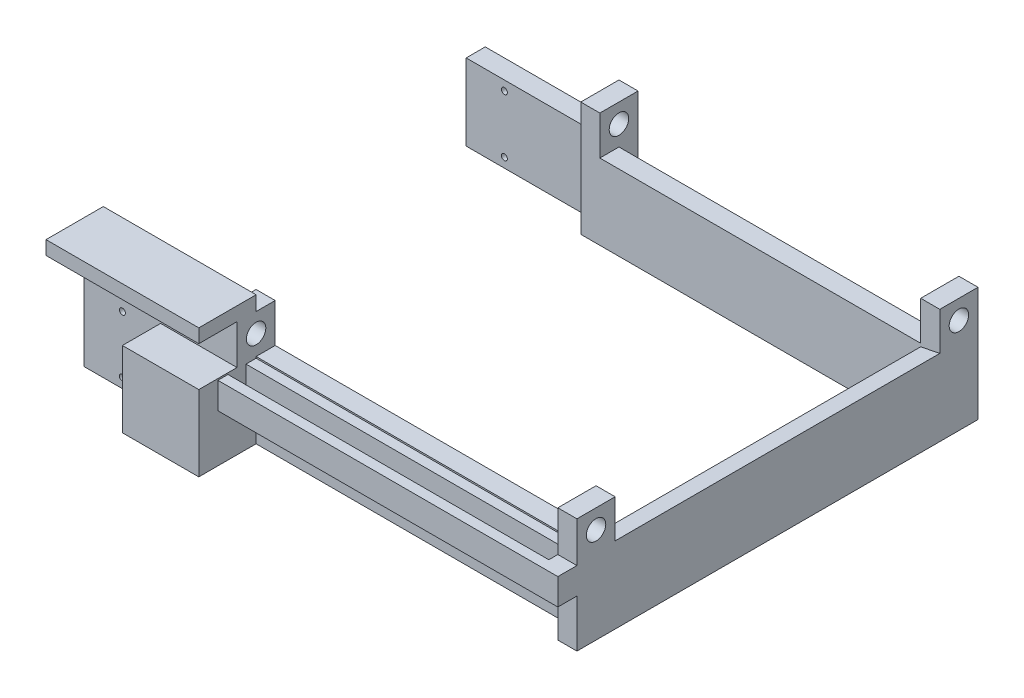
SolidWorks part; units mm, degrees
ref_plane "Front Plane" through (0, 0, 0) normal (0, 0, 1) x (1, 0, 0)
ref_plane "Top Plane" through (0, 0, 0) normal (0, 1, 0) x (1, 0, 0)
ref_plane "Right Plane" through (0, 0, 0) normal (1, 0, 0) x (0, 0, -1)
sketch "Sketch1" plane through (0, 0, 0) normal (0, 1, 0) x (1, 0, 0)
  line L0 (3.175, 114.3) -> (0, 114.3)
  line L1 (0, 0) -> (119.38, 0)
  line L2 (0, 0) -> (0, 6.35)
  line L3 (0, 120.65) -> (119.38, 120.65)
  line L4 (119.38, 0) -> (119.38, 120.65)
  line L5 (3.175, 114.3) -> (113.03, 114.3)
  line L7 (3.175, 6.35) -> (113.03, 6.35)
  line L8 (113.03, 114.3) -> (113.03, 6.35)
  line L9 (3.175, 6.35) -> (0, 6.35)
  line L10 (0, 114.3) -> (0, 120.65)
  dimension "D1" = 120.65
  dimension "D2" = 113.03
  dimension "D3" = 6.35
  dimension "D5" = 6.35
  dimension "D6" = 107.95
extrude "Boss-Extrude1" add sketch "Sketch1" along normal blind 25.4
sketch "Sketch2" plane through (0, 0, 0) normal (0, 0, 1) x (1, 0, 0)
  line L0 (119.38, 25.4) -> (113.03, 24.13)
  line L1 (113.03, 24.13) -> (113.03, 25.4)
  line L2 (0, 25.4) -> (119.38, 25.4) construction
  line L4 (113.03, 25.4) -> (119.38, 25.4)
  dimension "D2" = 1.27
extrude "Cut-Extrude1" cut sketch "Sketch2" against normal up to surface (114.3 mm away) from surface up to face at (56.515, 12.7, -114.3) starting at face at (56.515, 12.7, -6.35)
sketch "Sketch3" plane through (0, 0, 0) normal (0, 0, 1) x (1, 0, 0)
  line L0 (0, 25.4) -> (119.38, 25.4) construction
  line L1 (6.35, 25.4) -> (-44.45, 25.4)
  line L2 (6.35, 25.4) -> (6.35, 0)
  line L3 (6.35, 0) -> (-44.45, 0)
  line L4 (-44.45, 25.4) -> (-44.45, 0)
  line L5 (0, 25.4) -> (0, 0) construction
  dimension "D1" = 6.35
  dimension "D2" = 44.45
extrude "Boss-Extrude2" add sketch "Sketch3" along normal blind 6.35
extrude "Boss-Extrude3" add sketch "Sketch3<2>" against normal blind 6.35 from surface starting at face at (59.69, 12.7, -120.65)
sketch "Sketch3<2>" plane through (0, 0, 0) normal (0, 0, 1) x (1, 0, 0) same geometry as "Sketch3"
sketch "Sketch8" plane through (0, 25.4, 0) normal (0, 1, 0) x (1, 0, 0)
  line L0 (119.38, 60.325) -> (-5.0576, 60.325) construction
  line L1 (119.38, -6.35) -> (113.03, -6.35)
  line L2 (119.38, -6.35) -> (119.38, 6.35)
  line L4 (113.03, -6.35) -> (113.03, 6.35)
  line L5 (113.03, 6.35) -> (119.38, 6.35)
  line L6 (59.69, 114.3) -> (59.69, -20.9935) construction
  line L7 (0, 114.3) -> (119.38, 114.3) construction
  line L8 (119.38, 114.3) -> (119.38, 6.35) construction
  line L9 (6.35, -6.35) -> (6.35, 6.35)
  line L10 (0, 6.35) -> (6.35, 6.35)
  line L11 (0, -6.35) -> (0, 6.35)
  line L12 (0, -6.35) -> (6.35, -6.35)
  line L22 (0, 127) -> (6.35, 127)
  line L23 (0, 127) -> (0, 114.3)
  line L24 (0, 114.3) -> (6.35, 114.3)
  line L25 (6.35, 127) -> (6.35, 114.3)
  line L26 (113.03, 127) -> (113.03, 114.3)
  line L27 (119.38, 114.3) -> (113.03, 114.3)
  line L28 (119.38, 127) -> (119.38, 114.3)
  line L29 (119.38, 127) -> (113.03, 127)
  dimension "D1" = 12.7
extrude "Boss-Extrude4" add sketch "Sketch8" along normal blind 38.1 from surface starting at face at (19.5263, 0, -60.325)
sketch "Sketch9" plane through (119.38, 0, 0) normal (1, 0, 0) x (0, 0, -1)
  line L0 (-6.35, 38.1) -> (6.35, 38.1) construction
  line L3 (60.325, 36.7762) -> (60.325, 19.9574) construction
  line L4 (6.35, 38.1) -> (6.35, 0) construction
  line L5 (-6.35, 38.1) -> (-6.35, 0) construction
  circle A0 centre (0, 31.75) radius 3.2385
  circle A1 centre (120.65, 31.75) radius 3.2385
  dimension "D1" = 6.477
  dimension "D4" = 53.975
  dimension "D2" = 6.35
  dimension "D3" = 6.35
extrude "Cut-Extrude2" cut sketch "Sketch9" against normal through all both and the other way through all
sketch "Sketch10" plane through (0, 0, 6.35) normal (0, 0, 1) x (1, 0, 0)
  line L0 (0, 25.4) -> (-44.45, 25.4) construction
  line L1 (-44.45, 25.4) -> (-44.45, 0) construction
  circle A0 centre (-31.75, 22.225) radius 1
  circle A1 centre (-31.75, 3.175) radius 1
  dimension "D2" = 2
  dimension "D4" = 2
  dimension "D1" = 3.175
  dimension "D3" = 12.7
  dimension "D5" = 19.05
  dimension "D6" = 12.7
extrude "Cut-Extrude3" cut sketch "Sketch10" against normal through all
sketch "Sketch11" plane through (0, 0, 6.35) normal (0, 0, 1) x (1, 0, 0)
  line L0 (-44.45, 0) -> (6.35, 0) construction
  line L1 (6.35, 25.146) -> (-19.05, 25.146)
  line L2 (6.35, 25.146) -> (6.35, 0)
  line L3 (6.35, 0) -> (-19.05, 0)
  line L4 (-19.05, 25.146) -> (-19.05, 0)
  line L5 (0, 25.4) -> (-44.45, 25.4) construction
  dimension "D1" = 25.4
  dimension "D2" = 0.254
extrude "Boss-Extrude5" add sketch "Sketch11" along normal blind 12.7
sketch "Sketch13" plane through (0, 25.4, 0) normal (0, 1, 0) x (1, 0, 0)
  line L1 (-44.45, 0) -> (0, 0)
  line L2 (-44.45, 0) -> (-44.45, -6.35)
  line L3 (-44.45, -6.35) -> (0, -6.35)
  line L4 (0, 0) -> (0, -6.35)
extrude "Boss-Extrude6" add sketch "Sketch13" along normal up to surface (12.7 mm away) up to face at (3.175, 38.1, 0)
sketch "Sketch15" plane through (0, 0, 6.35) normal (0, 0, 1) x (1, 0, 0)
  line L0 (6.35, 25.146) -> (6.35, 38.1) construction
  line L1 (-44.45, 38.1) -> (6.35, 38.1)
  line L2 (-44.45, 38.1) -> (-44.45, 42.926)
  line L3 (-44.45, 42.926) -> (6.35, 42.926)
  line L4 (6.35, 38.1) -> (6.35, 42.926)
  dimension "D1" = 4.826
extrude "Boss-Extrude7" add sketch "Sketch15" along normal up to surface (12.7 mm away) from surface up to face at (-6.35, 12.573, 19.05) starting at face at (-32.75, 22.225, 0)
sketch "Sketch17" plane through (0, 0, 19.05) normal (0, 0, 1) x (1, 0, 0)
  line L0 (-44.45, 42.926) -> (-44.45, 38.1) construction
  line L1 (6.35, 38.1) -> (-44.45, 38.1)
  line L2 (6.35, 38.1) -> (6.35, 38.354)
  line L3 (6.35, 38.354) -> (-44.45, 38.354)
  line L4 (-44.45, 38.1) -> (-44.45, 38.354)
  dimension "D1" = 0.254
extrude "Cut-Extrude4" cut sketch "Sketch17" against normal up to surface (12.7 mm away) up to face at (-19.05, 21.082, 6.35)
sketch "Sketch19" plane through (6.35, 0, 0) normal (1, 0, 0) x (0, 0, -1)
  line L0 (-19.05, 25.146) -> (-6.35, 25.146) construction
  line L1 (-12.7, 24.638) -> (0, 24.638)
  line L2 (-12.7, 24.638) -> (-12.7, 15.875)
  line L3 (-12.7, 15.875) -> (0, 15.875)
  line L4 (0, 24.638) -> (0, 15.875)
  line L5 (-6.35, 38.1) -> (-6.35, 0) construction
  line L6 (-19.05, 0) -> (0, 0) construction
  dimension "D1" = 0.508
  dimension "D2" = 6.35
  dimension "D3" = 15.875
extrude "Boss-Extrude8" add sketch "Sketch19" along normal up to surface (113.03 mm away) up to face at (119.38, 31.75, 3.2385)
sketch "Sketch20" plane through (0, 0, 0) normal (0, 0, 1) x (1, 0, 0)
  line L1 (113.03, 25.4) -> (6.35, 25.4)
  line L2 (113.03, 25.4) -> (113.03, 25.146)
  line L3 (113.03, 25.146) -> (6.35, 25.146)
  line L19 (6.35, 25.4) -> (6.35, 25.146)
extrude "Cut-Extrude5" cut sketch "Sketch20" against normal through all
sketch "Sketch22" plane through (0, 24.638, 0) normal (0, 1, 0) x (1, 0, 0)
  line L2 (6.35, -3.35) -> (113.03, -3.35)
  line L3 (6.35, -3.35) -> (6.35, -9.35)
  line L4 (6.35, -9.35) -> (113.03, -9.35)
  line L5 (113.03, -3.35) -> (113.03, -9.35)
  line L6 (6.35, 0) -> (6.35, -12.7) construction
  line L7 (113.03, -6.35) -> (113.03, 0) construction
  point P6 (6.35, -6.35)
  point P7 (6.35, -6.35)
  dimension "D1" = 6
extrude "Cut-Extrude6" cut sketch "Sketch22" against normal through all
equation "\"tightTol\"= 0.005in"
equation "\"normTol\"= 0.01in"
equation "\"looseTol\"= 0.02in"
equation "\"D1@Sketch9\"=\"tightTol\"+0.250000in"
equation "\"D2@Sketch10\"=2mm"
equation "\"D4@Sketch10\"=2mm"
equation "\"D2@Sketch11\"=\"normTol\""
equation "\"D1@Sketch17\"=\"normTol\""
equation "\"D1@Sketch15\"=0.200000in-\"normTol\""
equation "\"D1@Sketch19\"=\"looseTol\""
equation "\"D1@Sketch22\"=6mm"
